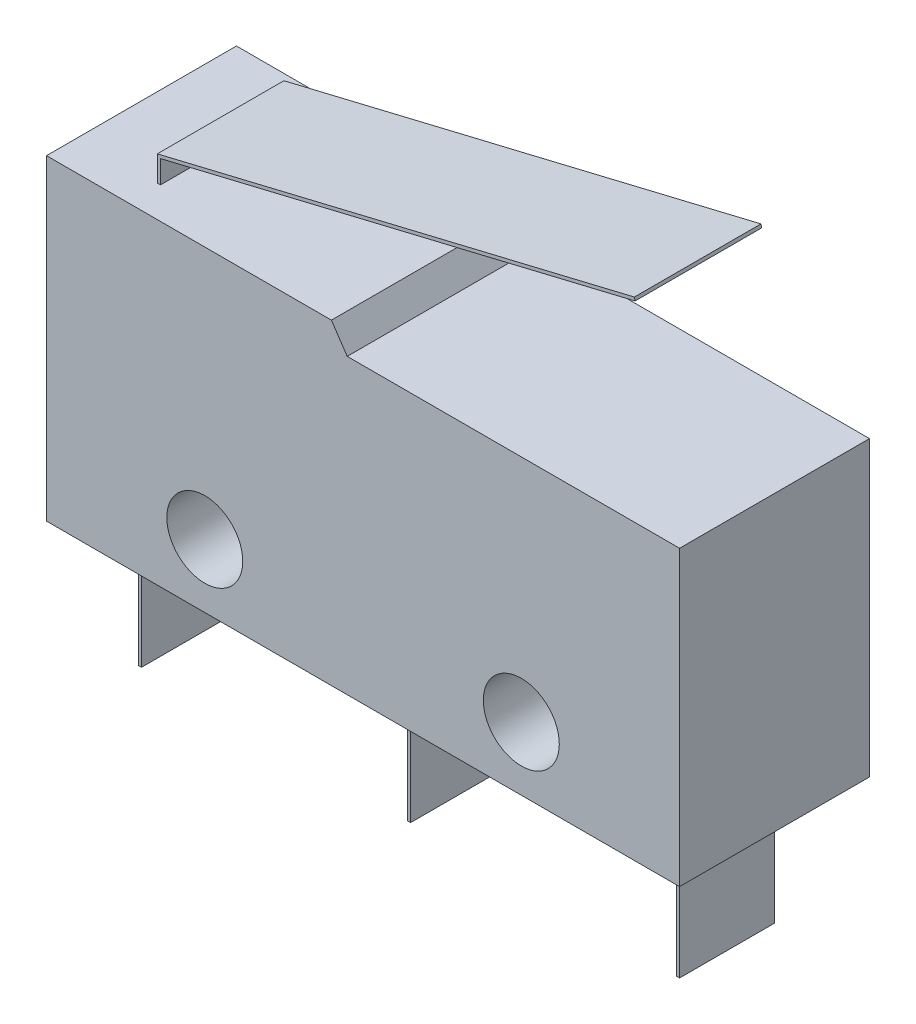
SolidWorks part; units mm, degrees
ref_plane "Front" through (0, 0, 0) normal (0, 0, 1) x (1, 0, 0)
ref_plane "Top" through (0, 0, 0) normal (0, 1, 0) x (1, 0, 0)
ref_plane "Right" through (0, 0, 0) normal (1, 0, 0) x (0, 0, -1)
sketch "Sketch1" plane through (0, 0, 0) normal (0, 0, 1) x (1, 0, 0)
  line L0 (-1, 5) -> (-0.5, 4.2583)
  line L1 (-10, 5) -> (10, 5)
  line L2 (-10, 5) -> (-10, -5)
  line L3 (-10, -5) -> (10, -5)
  line L4 (10, 5) -> (10, -5)
  line L5 (-10, 5) -> (10, -5) construction
  line L6 (-10, -5) -> (10, 5) construction
  line L7 (-0.5, 4.2583) -> (10, 4.2583)
  circle A0 centre (-5, -3) radius 1.2
  circle A1 centre (5, -3) radius 1.2
  point P0 (0, 0)
  dimension "D3" = 2.4
  dimension "D1" = 20
  dimension "D2" = 10
  dimension "D4" = 2
  dimension "D5" = 5
  dimension "D6" = 5
  dimension "D7" = 9
  dimension "D8" = 10.5
extrude "Boss-Extrude1" add sketch "Sketch1" along normal blind 6 contours L7 L0 L1 L2 L3 L4 A1 A0 region at (-0.2015, -0.0535, 0)
sketch "Sketch2" plane through (0, 0, 6) normal (0, 0, 1) x (1, 0, 0)
  line L0 (-7.5, 5) -> (-7.5, 5.8)
  line L2 (-7.5, 5.8) -> (7.5717, 9.4184)
  line L4 (-10, 5) -> (-1, 5) construction
  line L5 (-10, 5) -> (-10, -5) construction
  dimension "D1" = 0.8
  dimension "D2" = 13.5
  dimension "D3" = 15.5
  dimension "D4" = 2.5
extrude "Extrude-Thin1" add sketch "Sketch2" against normal blind 4 from offset 1 thin contours L0 L2 offset against normal yes thin type one direction wall 0.1
sketch "Sketch3" plane through (0, -5, 0) normal (0, -1, 0) x (1, 0, 0)
  line L0 (-8.5, 4.5) -> (-8.5, 1.5)
  line L1 (-10, 6) -> (-10, 0) construction
  line L2 (-10, 6) -> (10, 6) construction
  line L3 (0, -3.3) -> (0, 3.3) construction
  line L4 (8.5, 4.5) -> (8.5, 1.5)
  line L5 (0, 4.5) -> (0, 1.5)
  dimension "D1" = 3
  dimension "D2" = 1.5
  dimension "D3" = 1.5
extrude "Extrude-Thin2" add sketch "Sketch3" along normal blind 4 thin thin type one direction wall 0.1
